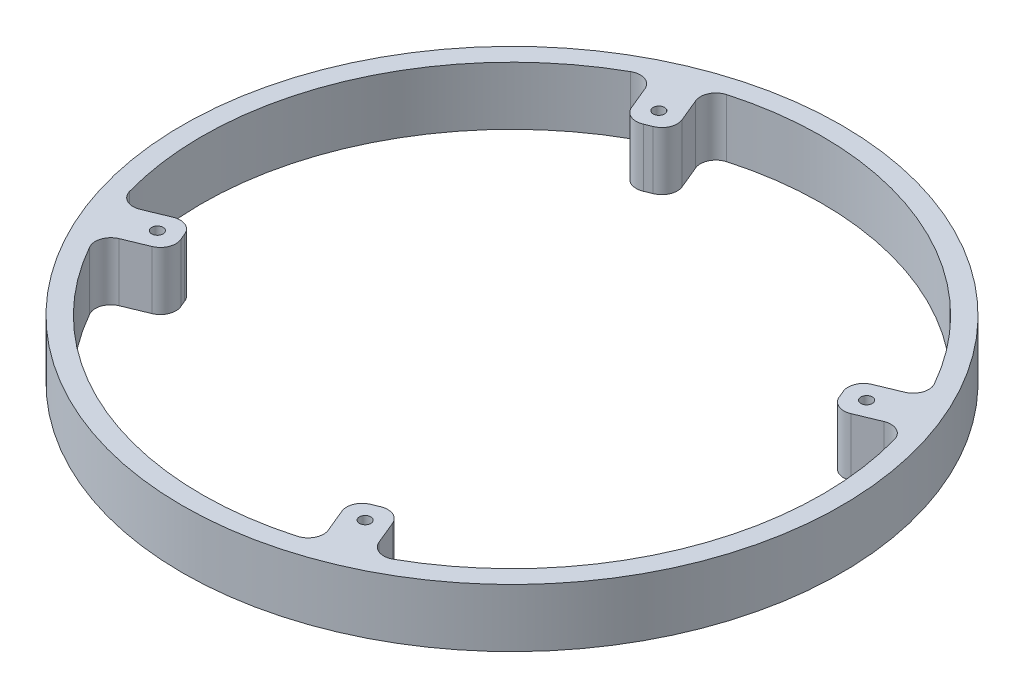
SolidWorks part; units mm, degrees
ref_plane "Front Plane" through (0, 0, 0) normal (0, 0, 1) x (1, 0, 0)
ref_plane "Top Plane" through (0, 0, 0) normal (0, 1, 0) x (1, 0, 0)
ref_plane "Right Plane" through (0, 0, 0) normal (1, 0, 0) x (0, 0, -1)
sketch "Sketch2" plane through (0, 0, 0) normal (1, 0, 0) x (0, 0, -1)
  line L0 (-65, 0) -> (-84.9998, 0)
  line L1 (-84.9998, 0) -> (-84.9998, 15)
  line L2 (-84.9998, 15) -> (-65, 15)
  line L5 (-65, 15) -> (-65, 0)
  dimension "D1" = 84.9998
  dimension "D2" = 15
  dimension "D3" = 65
ref_axis "Axis1" through (0, -0.75, 0) along (0, 1, 0)
revolve "Revolve1" add sketch "Sketch2" angle 360 about axis through (0, -0.75, 0) along (0, 1, 0)
hole_wizard "#32 (0.116) Diameter Hole1" positions "Sketch6" profile "Sketch7" hole size "#32" standard "ANSI Inch" end condition through all
sketch "Sketch6" plane through (0, 15, 0) normal (0, 1, 0) x (1, 0, 0)
  line L0 (0, 0) -> (-53.438, 129.0108) construction
  line L2 (0, 0) -> (0, 109.0908) construction
  point P0 (-26.7878, 64.6716)
  dimension "D1" = 22.5
  dimension "D2" = 70
sketch "Sketch7" plane through (-26.7878, 15, -64.6716) normal (1, 0, 0) x (0, 0, 1)
  line L0 (0, 0) -> (0, 15)
  line L1 (0, 15) -> (1.4732, 15)
  line L2 (1.4732, 15) -> (1.4732, 0)
  line L5 (1.4732, 0) -> (0, 0)
  line L11 (0, -6.35) -> (0, 107.95) construction
  dimension "Thru Hole Dia." = 2.9464
  dimension "Thru Hole Depth" = 15
pattern_circular "CirPattern3" count 4 over 360 about axis through (0, -0.75, 0) along (0, 1, 0) of "#32 (0.116) Diameter Hole1"
sketch "Sketch8" plane through (0, 15, 0) normal (0, 1, 0) x (1, 0, 0)
  line L0 (0, 0) -> (0, 111.8066) construction
  line L4 (0, 0) -> (35.0883, 84.7106) construction
  line L5 (0, 0) -> (113.8372, 0) construction
  line L6 (-4.7544, 24.5438) -> (-25.9354, 75.6791)
  line L7 (20.7169, 13.9932) -> (71.8523, 35.1742)
  line L8 (0, 0) -> (-26.7878, 64.6716) construction
  arc A0 (-4.7544, 24.5438) -> (20.7169, 13.9932) centre (0, 0) cw
  arc A1 (-25.9354, 75.6791) -> (71.8523, 35.1742) centre (0, 0) cw
  circle A2 centre (0, 0) radius 84.9998 construction
  dimension "D1" = 25
  dimension "D2" = 5
  dimension "D3" = 5
  dimension "D4" = 22.5
extrude "Cut-Extrude1" cut sketch "Sketch8" against normal through all
fillet "Fillet1" radius 4 4 edges at (71.8523, 7.5, -35.1742) (-25.9354, 7.5, -75.6791) (57.9608, 7.5, -29.4201) (-20.1813, 7.5, -61.7877)
pattern_circular "CirPattern4" count 4 over 360 about axis through (0, -0.75, 0) along (0, 1, 0) of "Cut-Extrude1", "Fillet1"
